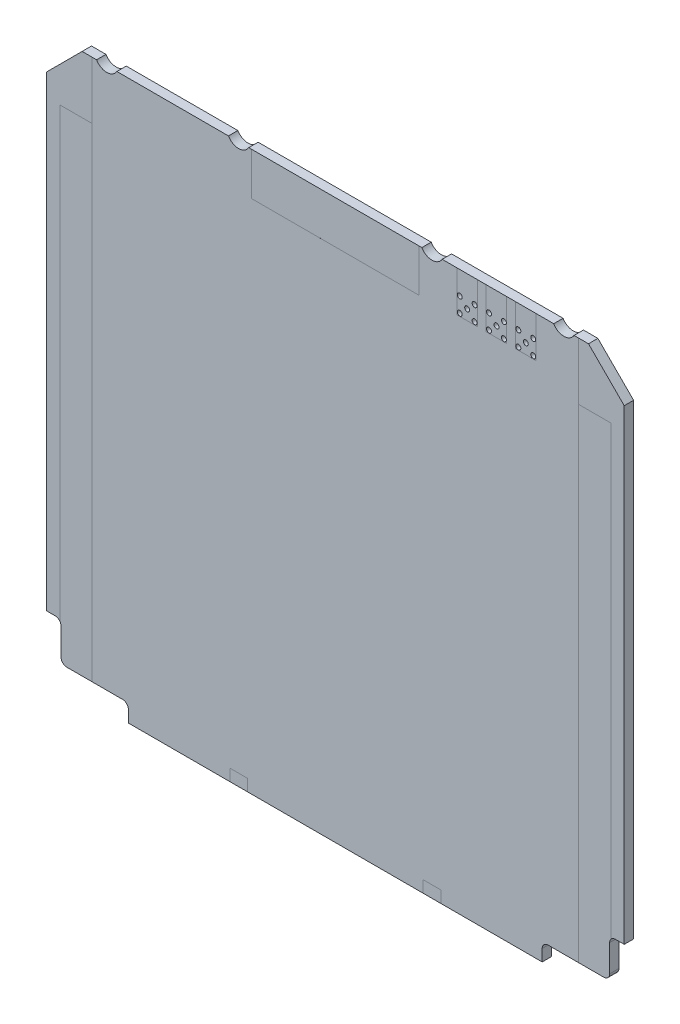
SolidWorks part; units mm, degrees
material "FR4_stuffedProtoboard"
ref_plane "Front Plane" through (0, 0, 0) normal (0, 0, 1) x (1, 0, 0)
ref_plane "Top Plane" through (0, 0, 0) normal (0, 1, 0) x (1, 0, 0)
ref_plane "Right Plane" through (0, 0, 0) normal (1, 0, 0) x (0, 0, -1)
ref_plane "Plane4" through (0, 0, -0.0125) normal (0, 0, -1) x (-1, 0, 0)
sketch "Sketch1" plane through (0, 0, -0.0125) normal (0, 0, -1) x (-1, 0, 0)
  line L4 (49.3, -50) -> (49.3, 45.3)
  line L6 (49.3, 45.3) -> (-49.3, 45.3)
  line L12 (-49.3, 45.3) -> (-49.3, -50)
  line L17 (-49.3, -50) -> (49.3, -50)
  line L18 (0, -50) -> (0, 45.3) construction
  dimension "D7" = 95.3
  dimension "D1" = 98.6
  dimension "D34" = 50
extrude "basicSize" add sketch "Sketch1" against normal blind 1.6
chamfer "Chamfer1" distance 6.1 angle 45 2 edges at (49.3, 45.3, 0.7875) (-49.3, 45.3, 0.7875)
sketch "Sketch4" plane through (0, 0, 1.5875) normal (0, 0, 1) x (1, 0, 0)
  line L1 (37.2679, 45.3) -> (40.7321, 45.3)
  line L7 (-43.2, 45.3) -> (43.2, 45.3) construction
  line L8 (49.3, 39.2) -> (49.3, -50) construction
  arc A0 (40.7321, 45.3) -> (37.2679, 45.3) centre (39, 46.3) cw
  point P5 (39, 44.3)
  dimension "D1" = 2
  dimension "D3" = 10.3
  dimension "D2" = 1
extrude "backplaneSideScrewCutout" cut sketch "Sketch4" against normal through all both and the other way through all
pattern_linear "LPattern3" count 2 spacing 22.5 along (-1, 0, 0) of "backplaneSideScrewCutout"
mirror "Mirror3" about plane through (0, 0, 0) normal (1, 0, 0) of "LPattern3"
sketch "Sketch6" plane through (0, 0, 1.5875) normal (0, 0, 1) x (1, 0, 0)
  line L0 (-49.3, -50) -> (-49.3, 39.2) construction
  line L1 (-49.3, -40.4) -> (-46.8, -40.4)
  line L2 (-49.3, -40.4) -> (-49.3, -50)
  line L4 (-46.8, -40.4) -> (-46.8, -47)
  line L5 (49.3, -50) -> (-49.3, -50) construction
  line L6 (-35.3, -50) -> (-49.3, -50)
  line L7 (-35.3, -50) -> (-35.3, -47)
  line L8 (-35.3, -47) -> (-46.8, -47)
  dimension "D1" = 2.5
  dimension "D2" = 3
  dimension "D3" = 9.6
  dimension "D4" = 14
extrude "Cut-Extrude4" cut sketch "Sketch6" against normal through all
fillet "Fillet1" radius 1 3 edges at (-35.3, -47, 0.7875) (-46.8, -47, 0.7875) (-46.8, -40.4, 0.7875)
mirror "Mirror1" about plane through (0, 0, 0) normal (1, 0, 0) of "Cut-Extrude4", "Fillet1"
sketch "Sketch5" plane through (0, 0, 1.5875) normal (0, 0, 1) x (1, 0, 0)
  line L0 (21.23, 41.37) -> (23.77, 38.83) construction
  line L1 (21.23, 38.83) -> (21.23, 41.37) construction
  line L2 (21.23, 41.37) -> (23.77, 41.37) construction
  line L4 (49.3, 39.2) -> (49.3, -40.4) construction
  line L5 (-14.7679, 45.3) -> (14.7679, 45.3) construction
  circle A0 centre (22.5, 40.1) radius 0.425
  circle A1 centre (21.23, 41.37) radius 0.425
  circle A3 centre (21.23, 38.83) radius 0.425
  circle A4 centre (23.77, 41.37) radius 0.425
  circle A5 centre (23.77, 38.83) radius 0.425
  dimension "D2" = 0.85
  dimension "D1" = 2.54
  dimension "D3" = 3.93
  dimension "D4" = 28.07
extrude "Cut-Extrude3" cut sketch "Sketch5" against normal through all
pattern_linear "LPattern2" count 3 spacing 5 along (1, 0, 0) of "Cut-Extrude3"
sketch "partFootprints" plane through (0, 0, 1.5875) normal (0, 0, 1) x (1, 0, 0)
  line L1 (18.2321, 45.3) -> (37.2679, 45.3) construction
  line L6 (20.75, 45.3) -> (20.75, 38.35)
  line L7 (20.75, 38.35) -> (24.25, 38.35)
  line L8 (24.25, 38.35) -> (24.25, 45.3)
  line L9 (24.25, 45.3) -> (20.75, 45.3)
  line L10 (25.75, 45.3) -> (25.75, 38.35)
  line L11 (25.75, 38.35) -> (29.25, 38.35)
  line L12 (29.25, 38.35) -> (29.25, 45.3)
  line L13 (29.25, 45.3) -> (25.75, 45.3)
  line L14 (30.75, 45.3) -> (30.75, 38.35)
  line L15 (30.75, 38.35) -> (34.25, 38.35)
  line L16 (34.25, 38.35) -> (34.25, 45.3)
  line L17 (34.25, 45.3) -> (30.75, 45.3)
  line L19 (32.5, 38.35) -> (32.5, 40.1) construction
  line L23 (22.5, 38.35) -> (22.5, 40.1) construction
  circle A2 centre (22.5, 40.1) radius 0.425 construction
  circle A5 centre (32.5, 40.1) radius 0.425 construction
  dimension "D1" = 1.75
  dimension "D8" = 3.5
  dimension "D6" = 3
extrude "MMCXfootprint" cut sketch "partFootprints" against normal blind 0.0001
sketch "Sketch7" plane through (0, 0, 1.5875) normal (0, 0, 1) x (1, 0, 0)
  line L0 (-14.2875, 45.5) -> (-14.2875, 39.912) construction
  line L1 (-14.2875, 45.3) -> (-14.2875, 38.007)
  line L2 (-12.2428, 38.007) -> (-11.8872, 38.007) construction
  line L3 (-14.2875, 38.007) -> (14.2875, 38.007)
  line L4 (14.2875, 45.5) -> (14.2875, 39.912) construction
  line L5 (14.2875, 45.3) -> (14.2875, 38.007)
  line L7 (-14.7679, 45.3) -> (14.7679, 45.3) construction
  line L8 (-14.2875, 45.3) -> (14.2875, 45.3)
extrude "TigerEyeFootprint" cut sketch "Sketch7" against normal blind 0.0001
sketch "thermalContacts_upper" plane through (0, 0, 1.5875) normal (0, 0, 1) x (1, 0, 0)
  line L0 (-49.3, -40.4) -> (-49.3, 39.2) construction
  line L1 (35.3, -50) -> (-35.3, -50) construction
  line L2 (-49.3, 45.3) -> (49.3, 45.3) construction
  line L3 (-47, 35.5) -> (-47, -41.5)
  line L5 (-41.5, 35.5) -> (-47, 35.5)
  line L18 (-41.5, 35.5) -> (-41.5, 47)
  line L23 (-41.5, 47) -> (-56.1922, 47)
  line L24 (-56.1922, 47) -> (-56.1922, -41.5)
  line L25 (-56.1922, -41.5) -> (-47, -41.5)
  dimension "D1" = 2.3
  dimension "D2" = 8.5
  dimension "D3" = 9.8
  dimension "D4" = 7.8
  dimension "D5" = 88.5
  dimension "D6" = 14.6922
extrude "keepOut_bottom" cut sketch "thermalContacts_upper" against normal blind 0.0001
sketch "Sketch3" plane through (0, 0, 1.5875) normal (0, 0, 1) x (1, 0, 0)
  line L0 (18.2321, 45.3) -> (20.75, 45.3) construction
  line L1 (-46.8, -46) -> (-46.8, -41.4) construction
  line L2 (-36.3, -47) -> (-45.8, -47) construction
  line L3 (-47, -40.8) -> (-47, 35.5) construction
  line L10 (0, -50) -> (0, 45.3) construction
  line L11 (35.3, -50) -> (-35.3, -50) construction
  line L13 (-41.5, 35.5) -> (-47, 35.5)
  line L14 (-45.8, -47) -> (-41.5, -47)
  line L15 (-46.8, -41.4) -> (-46.8, -46)
  line L16 (-47, 35.5) -> (-47, -40.8)
  line L17 (-41.5, -47) -> (-41.5, 35.5)
  arc A2 (-46.8, -41.4) -> (-47, -40.8) centre (-47.8, -41.4) ccw construction
  arc A3 (-46.8, -46) -> (-45.8, -47) centre (-45.8, -46) ccw construction
  arc A4 (-45.8, -47) -> (-46.8, -46) centre (-45.8, -46) cw
  arc A5 (-47, -40.8) -> (-46.8, -41.4) centre (-47.8, -41.4) cw
extrude "caution_top" cut sketch "Sketch3" against normal blind 0.0001
sketch "hold-downLocations" plane through (0, 0, 1.5875) normal (0, 0, 1) x (1, 0, 0)
  line L0 (-18, -48) -> (-15, -48) construction
  line L1 (-18, -48) -> (-15, -48) construction
  line L2 (15, -48) -> (18, -48) construction
  line L3 (15, -48) -> (18, -48)
  line L4 (18, -48) -> (18, -50)
  line L5 (35.3, -50) -> (-35.3, -50) construction
  line L6 (18, -50) -> (15, -50)
  line L7 (15, -50) -> (15, -48)
  line L8 (-15, -48) -> (-15, -50) construction
  line L9 (-15, -50) -> (-18, -50) construction
  line L10 (-18, -50) -> (-18, -48) construction
extrude "hold-downFootprints" cut sketch "hold-downLocations" against normal blind 0.0001
ref_plane "midplane_Z" through (0, 0, 0.7875) normal (0, 0, 1) x (1, 0, 0)
mirror "clearances_top-bottom" about plane through (0, 0, 0.7875) normal (0, 0, 1) of "hold-downFootprints", "caution_top", "keepOut_bottom"
mirror "clearances_side-side" about plane through (0, 0, 0) normal (1, 0, 0) of "clearances_top-bottom"
sketch "recommendedBuildArea" plane through (0, 0, 1.5875) normal (0, 0, 1) x (1, 0, 0)
  line L0 (41.5, 38.007) -> (41.5, 35.5) construction
  line L1 (-35.3, -45.5) -> (-47, -45.5) construction
  line L2 (-35.3, -47) -> (-35.3, -45.5) construction
  line L3 (35.3, -47) -> (35.3, -45.5) construction
  line L4 (14.2875, 45.3) -> (-14.2875, 45.3)
  line L5 (-14.2875, 45.3) -> (-14.2875, 38.007)
  line L6 (-14.2875, 38.007) -> (14.2875, 38.007)
  line L7 (-43.2, 45.3) -> (-49.3, 39.2)
  line L8 (-49.3, 39.2) -> (-49.3, -40.4)
  line L9 (-49.3, -40.4) -> (-47.8, -40.4)
  line L10 (-47, -40.8) -> (-47, 35.5)
  line L11 (-47, 35.5) -> (-41.5, 35.5)
  line L12 (-41.5, 35.5) -> (-41.5, 45.3)
  line L13 (-41.5, 45.3) -> (-43.2, 45.3)
  line L14 (35.3, -45.5) -> (47, -45.5) construction
  line L15 (38.5, 35.007) -> (38.5, 32.5)
  line L16 (38.5, 32.5) -> (44, 32.5)
  line L17 (-47, -45.5) -> (-47, 35.5) construction
  line L18 (-47, 35.5) -> (-41.5, 35.5) construction
  line L19 (-41.5, 35.5) -> (-41.5, 45.3) construction
  line L20 (44, 32.5) -> (44, -42.5)
  line L21 (14.2875, 38.007) -> (14.2875, 45.3)
  line L22 (32.3, -42.5) -> (44, -42.5)
  line L23 (-14.2875, 45.3) -> (-14.2875, 38.007)
  line L24 (-14.2875, 38.007) -> (41.5, 38.007)
  line L25 (32.3, -47) -> (32.3, -42.5)
  line L26 (32.3, -47) -> (32.3, -47)
  line L27 (21, -47) -> (32.3, -47)
  line L28 (21, -45) -> (21, -47)
  line L29 (41.5, 45.3) -> (41.5, 35.5)
  line L30 (41.5, 35.5) -> (47, 35.5)
  line L31 (47, 35.5) -> (47, -40.8)
  line L32 (47.8, -40.4) -> (49.3, -40.4)
  line L33 (49.3, -40.4) -> (49.3, 39.2)
  line L34 (49.3, 39.2) -> (43.2, 45.3)
  line L35 (43.2, 45.3) -> (41.5, 45.3)
  line L36 (12, -45) -> (21, -45)
  line L37 (41.5, 35.5) -> (47, 35.5) construction
  line L38 (47, 35.5) -> (47, -45.5) construction
  line L39 (12, -47) -> (12, -45)
  line L40 (-12, -47) -> (12, -47)
  line L41 (-12, -45) -> (-12, -47)
  line L42 (-21, -45) -> (-12, -45)
  line L43 (-21, -47) -> (-21, -45)
  line L44 (-32.3, -47) -> (-21, -47)
  line L45 (-32.3, -47) -> (-32.3, -47)
  line L46 (-32.3, -47) -> (-32.3, -42.5)
  line L47 (-32.3, -42.5) -> (-44, -42.5)
  line L48 (-44, -42.5) -> (-44, 32.5)
  line L49 (-44, 32.5) -> (-38.5, 32.5)
  line L50 (-38.5, 32.5) -> (-38.5, 42.3)
  line L51 (-17.2875, 42.3) -> (-38.5, 42.3)
  line L52 (-17.2875, 42.3) -> (-17.2875, 35.007)
  line L53 (-17.2875, 35.007) -> (38.5, 35.007)
  line L72 (-15, -48) -> (-15, -50)
  line L73 (-15, -50) -> (15, -50)
  line L74 (15, -50) -> (15, -48)
  line L75 (15, -48) -> (18, -48)
  line L76 (18, -48) -> (18, -50)
  line L77 (18, -50) -> (35.3, -50)
  line L78 (35.3, -50) -> (35.3, -48)
  line L79 (36.3, -47) -> (41.5, -47)
  line L80 (41.5, -47) -> (41.5, 45.3)
  line L81 (41.5, 45.3) -> (40.7321, 45.3)
  line L82 (37.2679, 45.3) -> (34.25, 45.3)
  line L83 (34.25, 45.3) -> (34.25, 38.35)
  line L84 (34.25, 38.35) -> (30.75, 38.35)
  line L85 (30.75, 38.35) -> (30.75, 45.3)
  line L86 (30.75, 45.3) -> (29.25, 45.3)
  line L87 (29.25, 45.3) -> (29.25, 38.35)
  line L88 (29.25, 38.35) -> (25.75, 38.35)
  line L89 (25.75, 38.35) -> (25.75, 45.3)
  line L90 (25.75, 45.3) -> (24.25, 45.3)
  line L91 (24.25, 45.3) -> (24.25, 38.35)
  line L92 (24.25, 38.35) -> (20.75, 38.35)
  line L93 (20.75, 38.35) -> (20.75, 45.3)
  line L94 (20.75, 45.3) -> (18.2321, 45.3)
  line L95 (14.7679, 45.3) -> (14.2875, 45.3)
  line L96 (14.2875, 45.3) -> (14.2875, 38.007)
  line L97 (14.2875, 38.007) -> (-14.2875, 38.007)
  line L98 (-14.2875, 38.007) -> (-14.2875, 45.3)
  line L99 (-14.2875, 45.3) -> (-14.7679, 45.3)
  line L100 (-18.2321, 45.3) -> (-37.2679, 45.3)
  line L101 (-40.7321, 45.3) -> (-41.5, 45.3)
  line L102 (-41.5, 45.3) -> (-41.5, -47)
  line L103 (-41.5, -47) -> (-36.3, -47)
  line L104 (-35.3, -48) -> (-35.3, -50)
  line L105 (-35.3, -50) -> (-18, -50)
  line L106 (-18, -50) -> (-18, -48)
  line L107 (-18, -48) -> (-15, -48)
  line L108 (-15, -48) -> (-15, -50) construction
  line L109 (-15, -50) -> (15, -50) construction
  line L110 (15, -50) -> (15, -48) construction
  line L111 (15, -48) -> (18, -48) construction
  line L112 (18, -48) -> (18, -50) construction
  line L113 (18, -50) -> (35.3, -50) construction
  line L114 (35.3, -50) -> (35.3, -47) construction
  line L115 (35.3, -47) -> (41.5, -47) construction
  line L133 (41.5, 38.007) -> (-14.2875, 38.007)
  line L134 (-14.2875, 38.007) -> (-14.2875, 45.3)
  line L136 (-14.2875, 45.3) -> (-41.5, 45.3) construction
  line L139 (-41.5, -47) -> (-35.3, -47) construction
  line L140 (-35.3, -47) -> (-35.3, -50) construction
  line L141 (-35.3, -50) -> (-18, -50) construction
  line L142 (-18, -50) -> (-18, -48) construction
  line L143 (-18, -48) -> (-15, -48) construction
  arc A1 (-47, -40.8) -> (-47.8, -40.4) centre (-47.8, -41.4) ccw
  arc A3 (47.8, -40.4) -> (47, -40.8) centre (47.8, -41.4) ccw
  arc A10 (36.3, -47) -> (35.3, -48) centre (36.3, -48) ccw
  arc A11 (37.2679, 45.3) -> (40.7321, 45.3) centre (39, 46.3) ccw
  arc A12 (14.7679, 45.3) -> (18.2321, 45.3) centre (16.5, 46.3) ccw
  arc A13 (-18.2321, 45.3) -> (-14.7679, 45.3) centre (-16.5, 46.3) ccw
  arc A14 (-40.7321, 45.3) -> (-37.2679, 45.3) centre (-39, 46.3) ccw
  arc A15 (-35.3, -48) -> (-36.3, -47) centre (-36.3, -48) ccw
  point P36 (47, -43.9107)
  dimension "D5" = 1.5
  dimension "D1" = 0
  dimension "D2" = 0
  dimension "D3" = 0
  dimension "D4" = 0
  dimension "D6" = 3
ref_point "rail midpoint"
sketch "locatorSketch" plane through (0, 0, 1.5875) normal (0, 0, 1) x (1, 0, 0)
  line L0 (-12.2428, 39.531) -> (12.2428, 38.007) construction
  line L1 (12.2428, 39.531) -> (-12.2428, 38.007) construction
  line L4 (-12.2428, 38.261) -> (-12.2428, 38.007)
  line L5 (-11.8872, 38.261) -> (-12.2428, 38.261)
  line L6 (-11.8872, 38.007) -> (-11.8872, 38.261)
  line L7 (-12.2428, 38.007) -> (-11.8872, 38.007)
  line L8 (-12.2428, 38.261) -> (-12.2428, 38.007)
  line L9 (-11.8872, 38.261) -> (-12.2428, 38.261)
  line L10 (-11.8872, 38.007) -> (-11.8872, 38.261)
  line L11 (-12.2428, 38.007) -> (-11.8872, 38.007)
  line L12 (-12.2428, 39.531) -> (-12.2428, 39.277)
  line L13 (-11.8872, 39.531) -> (-12.2428, 39.531)
  line L14 (-11.8872, 39.277) -> (-11.8872, 39.531)
  line L15 (-12.2428, 39.277) -> (-11.8872, 39.277)
  line L16 (-12.2428, 39.531) -> (-12.2428, 39.277)
  line L17 (-11.8872, 39.531) -> (-12.2428, 39.531)
  line L18 (-11.8872, 39.277) -> (-11.8872, 39.531)
  line L19 (-12.2428, 39.277) -> (-11.8872, 39.277)
  line L20 (11.8872, 39.531) -> (11.8872, 39.277)
  line L21 (12.2428, 39.531) -> (11.8872, 39.531)
  line L22 (12.2428, 39.277) -> (12.2428, 39.531)
  line L23 (11.8872, 39.277) -> (12.2428, 39.277)
  line L24 (11.8872, 39.531) -> (11.8872, 39.277)
  line L25 (12.2428, 39.531) -> (11.8872, 39.531)
  line L26 (12.2428, 39.277) -> (12.2428, 39.531)
  line L27 (11.8872, 39.277) -> (12.2428, 39.277)
  line L28 (11.8872, 38.261) -> (11.8872, 38.007)
  line L29 (12.2428, 38.261) -> (11.8872, 38.261)
  line L30 (12.2428, 38.007) -> (12.2428, 38.261)
  line L31 (11.8872, 38.007) -> (12.2428, 38.007)
  line L32 (11.8872, 38.261) -> (11.8872, 38.007)
  line L33 (12.2428, 38.261) -> (11.8872, 38.261)
  line L34 (12.2428, 38.007) -> (12.2428, 38.261)
  line L35 (11.8872, 38.007) -> (12.2428, 38.007)
  dimension "D1" = 0
  dimension "D2" = 0
  dimension "D3" = 0
  dimension "D4" = 0
